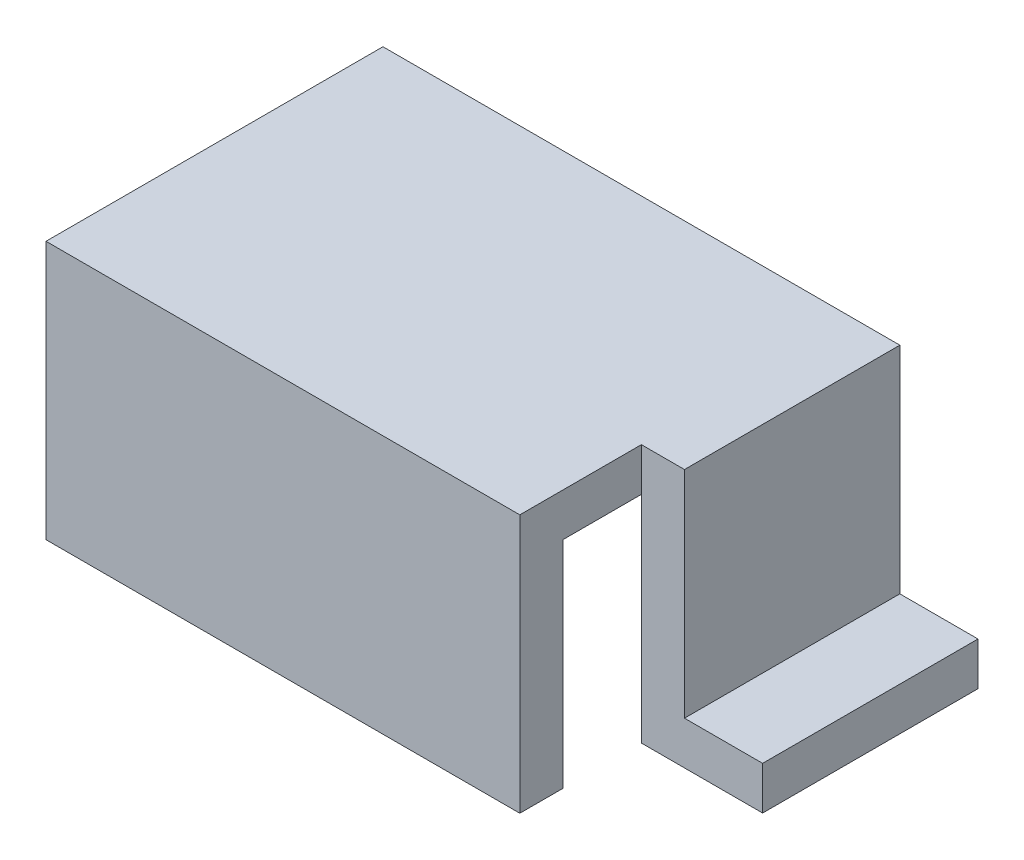
SolidWorks part; units mm, degrees
ref_plane "Front Plane" through (0, 0, 0) normal (0, 0, 1) x (1, 0, 0)
ref_plane "Top Plane" through (0, 0, 0) normal (0, 1, 0) x (1, 0, 0)
ref_plane "Right Plane" through (0, 0, 0) normal (1, 0, 0) x (0, 0, -1)
sketch "Sketch1" plane through (0, 0, 0) normal (0, 0, 1) x (1, 0, 0)
  line L5 (0, 0) -> (11.2575, 0)
  line L6 (11.2575, 0) -> (11.2575, 20)
  line L10 (11.2575, 20) -> (51.2575, 20)
  line L11 (51.2575, 20) -> (51.2575, 0)
  line L12 (51.2575, 0) -> (62.515, 0)
  line L13 (0, 4) -> (7.2575, 4)
  line L14 (7.2575, 4) -> (7.2575, 24)
  line L15 (7.2575, 24) -> (55.2575, 24)
  line L16 (55.2575, 24) -> (55.2575, 4)
  line L17 (55.2575, 4) -> (62.515, 4)
  line L18 (0, 0) -> (0, 4)
  line L19 (62.515, 0) -> (62.515, 4)
  dimension "D1" = 40
  dimension "D2" = 20
  dimension "D3" = 4
extrude "Boss-Extrude1" add sketch "Sketch1" along normal blind 20
sketch "Sketch2" plane through (7.2575, 0, 0) normal (-1, 0, 0) x (0, 0, 1)
  line L0 (20, 20) -> (27.29, 20)
  line L1 (20, 24) -> (20, 4) construction
  line L2 (27.29, 20) -> (27.29, 0)
  line L3 (26.29, 18) -> (26.29, 2.19) construction
  line L4 (20, 24) -> (31.29, 24)
  line L5 (31.29, 24) -> (31.29, 0)
  line L6 (20, 20) -> (20, 24)
  line L7 (27.29, 0) -> (31.29, 0)
  line L8 (27.29, 0) -> (20, 0)
  line L9 (20, 0) -> (20, 20)
  line L10 (20, 0) -> (0, 0) construction
  line L11 (20, 20) -> (20, 0)
  line M11 (20, 4) -> (20, 24)
  dimension "D1" = 4
  dimension "D2" = 1
  dimension "D3" = 4
extrude "Boss-Extrude2" add sketch "Sketch2" against normal up to surface (4 mm away) contours L9 L8 L2 L0 M11 | L2 L7 L5 L4 L0 M11 region at (7.2575, 14.3298, 27.9748) region at (7.2575, 10, 23.645) up to face at (11.2575, 10, 10)
extrude "Boss-Extrude3" add sketch "Sketch2<3>" against normal up to surface (44 mm away) contours L2 L7 L5 L4 L0 M11 region at (7.2575, 14.3298, 27.9748) up to face at (51.2575, 10, 10)
sketch "Sketch2<3>" plane through (7.2575, 0, 0) normal (-1, 0, 0) x (0, 0, 1) same geometry as "Sketch2"
